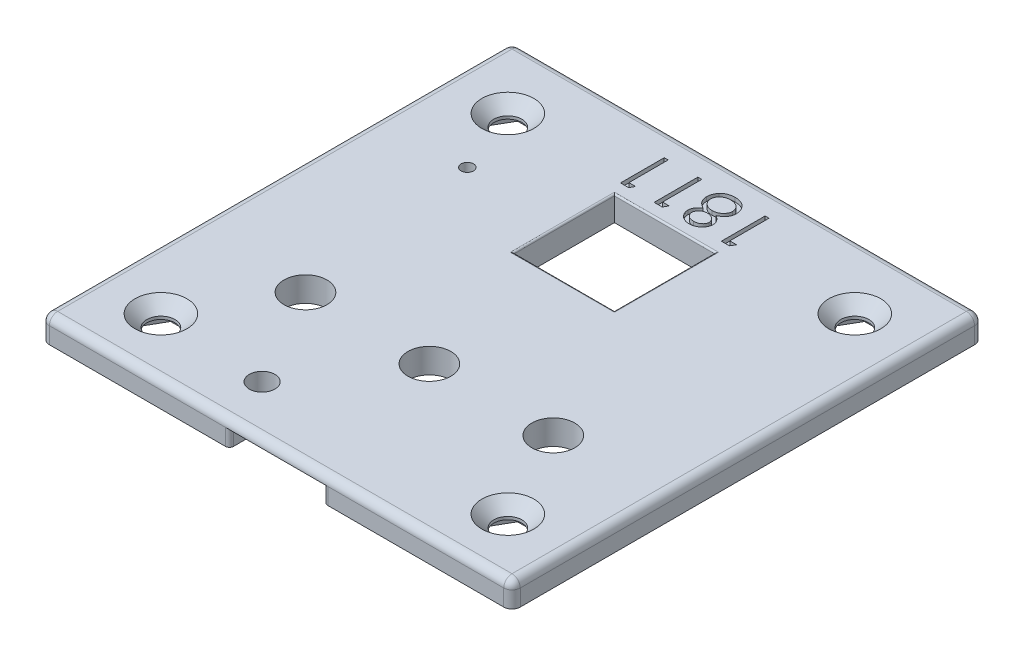
SolidWorks part; units mm, degrees
ref_plane "Plan de face" through (0, 0, 0) normal (0, 0, 1) x (1, 0, 0)
ref_plane "Plan de dessus" through (0, 0, 0) normal (0, 1, 0) x (1, 0, 0)
ref_plane "Plan de droite" through (0, 0, 0) normal (1, 0, 0) x (0, 0, -1)
sketch "Esquisse1" plane through (0, 0, 0) normal (0, 1, 0) x (1, 0, 0)
  line L1 (-29.9798, 40.399) -> (27.0202, 40.399)
  line L2 (-29.9798, 40.399) -> (-29.9798, -16.601)
  line L3 (-29.9798, -16.601) -> (27.0202, -16.601)
  line L4 (27.0202, 40.399) -> (27.0202, -16.601)
extrude "Boss.-Extru.1" add sketch "Esquisse1" along normal blind 3
sketch "Esquisse2" plane through (0, 3, 0) normal (0, 1, 0) x (1, 0, 0)
  line L0 (27.0202, -16.601) -> (27.0202, 40.399) construction
  line L1 (-29.9798, -16.601) -> (27.0202, -16.601) construction
  line L2 (-29.9798, 40.399) -> (-29.9798, -16.601) construction
  line L3 (27.0202, 40.399) -> (-29.9798, 40.399) construction
  circle A0 centre (19.5202, -9.601) radius 1.7
  circle A1 centre (-22.4798, -9.601) radius 1.7
  circle A2 centre (-22.4798, 32.399) radius 1.7
  circle A3 centre (19.5202, 32.399) radius 1.7
  dimension "D1" = 7.5
  dimension "D3" = 7.5
  dimension "D5" = 7.5
  dimension "D7" = 7.5
  dimension "D2" = 7
  dimension "D4" = 7
  dimension "D6" = 8
  dimension "D8" = 8
extrude "Enlèv. mat.-Extru.1" cut sketch "Esquisse2" against normal blind 3
sketch "Esquisse3" plane through (0, 3, 0) normal (0, 1, 0) x (1, 0, 0)
  line L0 (-29.9798, -16.601) -> (27.0202, -16.601) construction
  line L1 (-29.9798, 40.399) -> (-29.9798, -16.601) construction
  circle A0 centre (-9.2298, -10.601) radius 1.55
  dimension "D1" = 6
  dimension "D2" = 20.75
extrude "Enlèv. mat.-Extru.2" cut sketch "Esquisse3" against normal blind 3
sketch "Esquisse4" plane through (0, 3, 0) normal (0, 1, 0) x (1, 0, 0)
  line L1 (-7.5798, 30.399) -> (4.6202, 30.399)
  line L2 (-7.5798, 30.399) -> (-7.5798, 18.199)
  line L3 (-7.5798, 18.199) -> (4.6202, 18.199)
  line L4 (4.6202, 30.399) -> (4.6202, 18.199)
  line L5 (27.0202, 40.399) -> (-29.9798, 40.399) construction
  line L6 (-29.9798, 40.399) -> (-29.9798, -16.601) construction
  line L7 (-29.9798, -16.601) -> (27.0202, -16.601) construction
  line L8 (27.0202, -16.601) -> (27.0202, 40.399) construction
  circle A0 centre (-0.9798, 1.399) radius 2.6
  circle A2 centre (-15.9798, 1.399) radius 2.6
  circle A3 centre (14.0202, 1.399) radius 2.6
  dimension "D3" = 18
  dimension "D4" = 18
  dimension "D7" = 18
  dimension "D1" = 10
  dimension "D2" = 22.4
  dimension "D5" = 15
  dimension "D6" = 28
  dimension "D8" = 15
extrude "Enlèv. mat.-Extru.3" cut sketch "Esquisse4" against normal blind 3
fillet "Congé1" radius 1 1 edges at (-1.4798, 3, 16.601)
fillet "Congé2" radius 1 3 edges at (-29.9798, 1, 16.601) (-29.9798, 2.7071, 16.3081) (-29.9798, 3, -12.399)
fillet "Congé3" radius 1 3 edges at (27.0202, 1, 16.601) (27.0202, 2.7071, 16.3081) (27.0202, 3, -12.399)
fillet "Congé4" radius 1 5 edges at (27.0202, 1, -40.399) (26.7273, 2.7071, -40.399) (-29.9798, 1, -40.399) (-29.687, 2.7071, -40.399) (-1.4798, 3, -40.399)
fillet "Congé5" radius 0.2 1 edges at (-1.4798, 3, -30.399)
fillet "Congé6" radius 0.2 1 edges at (-7.5798, 3, -24.399)
fillet "Congé7" radius 0.2 1 edges at (4.6202, 3, -24.399)
fillet "Congé8" radius 0.2 1 edges at (-1.4798, 3, -18.199)
sketch "Esquisse11" plane through (0, 3, 0) normal (0, 1, 0) x (1, 0, 0)
  line L0 (-29.9798, -15.601) -> (-29.9798, 39.399) construction
  line L1 (-28.9798, 40.399) -> (26.0202, 40.399) construction
  circle A0 centre (-19.2798, 24.289) radius 0.75
  dimension "D1" = 10.7
  dimension "D2" = 16.11
extrude "Enlèv. mat.-Extru.5" cut sketch "Esquisse11" against normal blind 3
sketch "Esquisse12" plane through (0, 0, 16.601) normal (0, 0, 1) x (1, 0, 0)
  line L0 (-28.9798, 0) -> (26.0202, 0) construction
  line L1 (-7.1798, 0) -> (4.2202, 0)
  line L2 (-7.1798, 0) -> (-7.1798, 2)
  line L3 (-7.1798, 2) -> (4.2202, 2)
  line L4 (4.2202, 0) -> (4.2202, 2)
  line L5 (-29.9798, 0) -> (-29.9798, 2) construction
  line L6 (27.0202, 2) -> (27.0202, 0) construction
  dimension "D1" = 22.8
  dimension "D2" = 22.8
extrude "Enlèv. mat.-Extru.6" cut sketch "Esquisse12" against normal blind 2
sketch "Esquisse13" plane through (0, 3, 0) normal (0, 1, 0) x (1, 0, 0)
  text T0 "<r180>1181</r>" font "Century Gothic" height in points 20
extrude "Enlèv. mat.-Extru.7" cut sketch "Esquisse13" against normal blind 0.5
fillet "Congé9" radius 0.5 1 edges at (4.2202, 1, 16.601)
fillet "Congé11" radius 0.5 1 edges at (-7.1798, 1, 16.601)
hole_wizard "Fraisage pour vis à tête fraisée M31" positions "Esquisse16" profile "Esquisse17" countersink size "M3" standard "Ansi Metric" end condition through all
sketch "Esquisse16" plane through (0, 3, 0) normal (0, 1, 0) x (1, 0, 0)
  point P0 (-22.4798, 32.399)
  point P3 (-22.4798, -9.601)
  point P6 (19.5202, 32.399)
  point P9 (19.5202, -9.601)
sketch "Esquisse17" plane through (-22.4798, 3, -32.399) normal (1, 0, 0) x (0, 0, 1)
  line L0 (0, 0) -> (0, 3)
  line L1 (0, 3) -> (1.7, 3)
  line L2 (1.7, 3) -> (1.7, 1.45)
  line L3 (1.7, 1.45) -> (3.15, 0)
  line L5 (3.15, 0) -> (0, 0)
  line L6 (-1.7, 1.45) -> (-3.15, 0) construction
  line L11 (0, -6.35) -> (0, 107.95) construction
  dimension "Diamètre du perçage jusqu'au prochain" = 3.4
  dimension "Profondeur du perçage jusqu'au prochain" = 3
  dimension "Diamètre du fraisage entrant" = 6.3
  dimension "Angle du fraisage entrant" = 90
sketch "Esquisse18" plane through (0, 0, 0) normal (0, -1, 0) x (-1, 0, 0)
  line L1 (24.0798, -12.3723) -> (25.6798, -9.601)
  line L2 (25.6798, -9.601) -> (24.0798, -6.8297)
  line L3 (24.0798, -6.8297) -> (20.8798, -6.8297)
  line L4 (20.8798, -6.8297) -> (19.2798, -9.601)
  line L5 (19.2798, -9.601) -> (20.8798, -12.3723)
  line L6 (20.8798, -12.3723) -> (24.0798, -12.3723)
  circle A0 centre (22.4798, -9.601) radius 2.7713 construction
  circle A1 centre (22.4798, -9.601) radius 1.7 construction
  dimension "D1" = 0
extrude "Enlèv. mat.-Extru.8" cut sketch "Esquisse18" against normal blind 1.2 contours L6 L1 L2 L3 L4 L5
sketch "Esquisse19" plane through (0, 0, 0) normal (0, -1, 0) x (-1, 0, 0)
  line L0 (-26.0202, 40.399) -> (28.9798, 40.399) construction
  line L1 (24.0798, 35.1703) -> (20.8798, 35.1703)
  line L2 (20.8798, 35.1703) -> (19.2798, 32.399)
  line L3 (19.2798, 32.399) -> (20.8798, 29.6277)
  line L4 (20.8798, 29.6277) -> (24.0798, 29.6277)
  line L5 (24.0798, 29.6277) -> (25.6798, 32.399)
  line L6 (25.6798, 32.399) -> (24.0798, 35.1703)
  circle A0 centre (22.4798, 32.399) radius 2.7713 construction
  circle A1 centre (22.4798, 32.399) radius 1.7 construction
  dimension "D1" = 0
extrude "Enlèv. mat.-Extru.9" cut sketch "Esquisse19" against normal blind 1.2
sketch "Esquisse20" plane through (0, 0, 0) normal (0, -1, 0) x (-1, 0, 0)
  line L0 (-26.0202, 40.399) -> (28.9798, 40.399) construction
  line L1 (-17.9202, 35.1703) -> (-21.1202, 35.1703)
  line L2 (-21.1202, 35.1703) -> (-22.7202, 32.399)
  line L3 (-22.7202, 32.399) -> (-21.1202, 29.6277)
  line L4 (-21.1202, 29.6277) -> (-17.9202, 29.6277)
  line L5 (-17.9202, 29.6277) -> (-16.3202, 32.399)
  line L6 (-16.3202, 32.399) -> (-17.9202, 35.1703)
  circle A0 centre (-19.5202, 32.399) radius 2.7713 construction
  circle A1 centre (-19.5202, 32.399) radius 1.7 construction
  dimension "D1" = 0
extrude "Enlèv. mat.-Extru.10" cut sketch "Esquisse20" against normal blind 1.2
sketch "Esquisse21" plane through (0, 0, 0) normal (0, -1, 0) x (-1, 0, 0)
  line L0 (-4.7202, -16.601) -> (-26.0202, -16.601) construction
  line L1 (-21.1202, -6.8297) -> (-22.7202, -9.601)
  line L2 (-22.7202, -9.601) -> (-21.1202, -12.3723)
  line L3 (-21.1202, -12.3723) -> (-17.9202, -12.3723)
  line L4 (-17.9202, -12.3723) -> (-16.3202, -9.601)
  line L5 (-16.3202, -9.601) -> (-17.9202, -6.8297)
  line L6 (-17.9202, -6.8297) -> (-21.1202, -6.8297)
  circle A0 centre (-19.5202, -9.601) radius 2.7713 construction
  circle A1 centre (-19.5202, -9.601) radius 1.7 construction
  dimension "D1" = 0
extrude "Enlèv. mat.-Extru.11" cut sketch "Esquisse21" against normal blind 1.2
sketch "Esquisse22" plane through (0, 0, 0) normal (0, -1, 0) x (-1, 0, 0)
  line L1 (-10.2202, -0.821) -> (-5.2202, -0.821)
  line L2 (-10.2202, -0.821) -> (-10.2202, 10.219)
  line L3 (-10.2202, 10.219) -> (-5.2202, 10.219)
  line L4 (-5.2202, -0.821) -> (-5.2202, 10.219)
  circle A1 centre (22.4798, -9.601) radius 1.7 construction
  point P4 (0, 0)
  dimension "D2" = 19.82
  dimension "D1" = 32.7
extrude "Enlèv. mat.-Extru.12" cut sketch "Esquisse22" against normal blind 1
